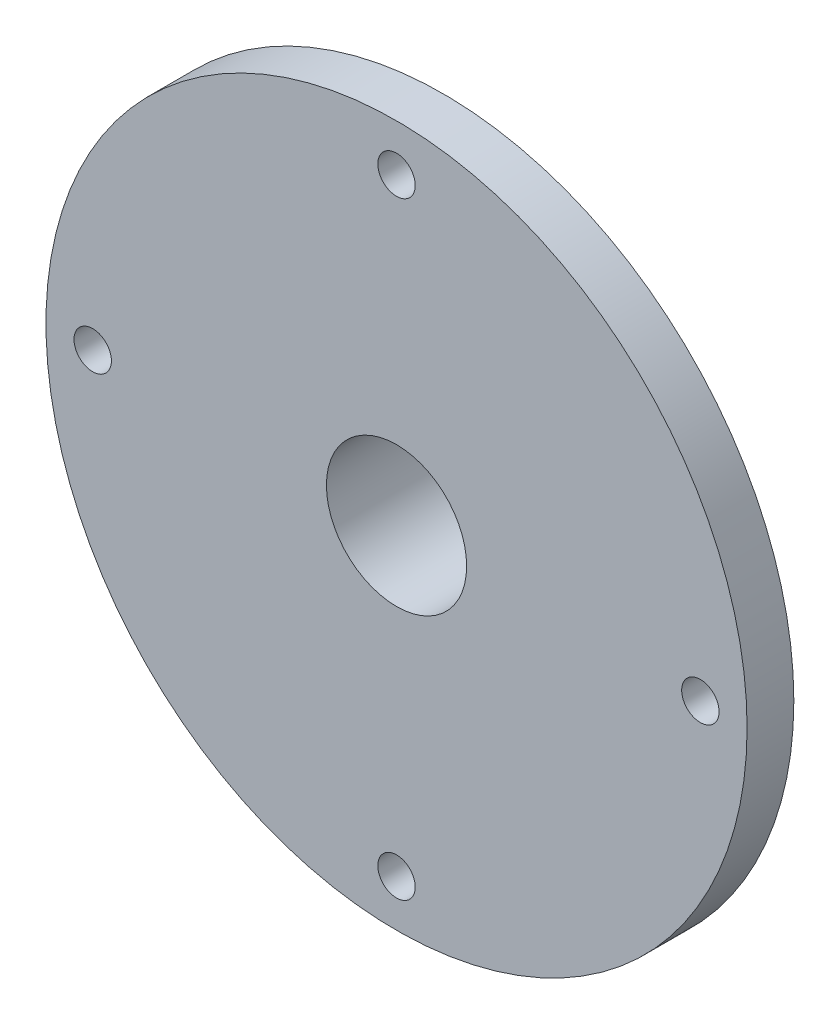
SolidWorks part; units mm, degrees
ref_plane "Front Plane" through (0, 0, 0) normal (0, 0, 1) x (1, 0, 0)
ref_plane "Top Plane" through (0, 0, 0) normal (0, 1, 0) x (1, 0, 0)
ref_plane "Right Plane" through (0, 0, 0) normal (1, 0, 0) x (0, 0, -1)
sketch "Sketch1" plane through (0, 0, 0) normal (0, 0, 1) x (1, 0, 0)
  circle A3 centre (0, 0) radius 15
  circle A4 centre (0, 0) radius 75 construction
  circle A5 centre (0, 0) radius 75
  circle A6 centre (0, 65) radius 4 construction
  circle A7 centre (0, 65) radius 4
  circle A8 centre (-65, 0) radius 4 construction
  circle A9 centre (0, -65) radius 4 construction
  circle A10 centre (65, 0) radius 4 construction
  circle A11 centre (-65, 0) radius 4
  circle A12 centre (0, -65) radius 4
  circle A13 centre (65, 0) radius 4
extrude "Boss-Extrude1" add sketch "Sketch1" along normal blind 10
sketch "Sketch2" plane through (0, 0, 0) normal (0, 0, -1) x (-1, 0, 0)
  circle A1 centre (0, 0) radius 24
  circle A2 centre (0, 0) radius 15 construction
  circle A3 centre (0, 0) radius 15
extrude "Boss-Extrude2" add sketch "Sketch2" along normal blind 25
